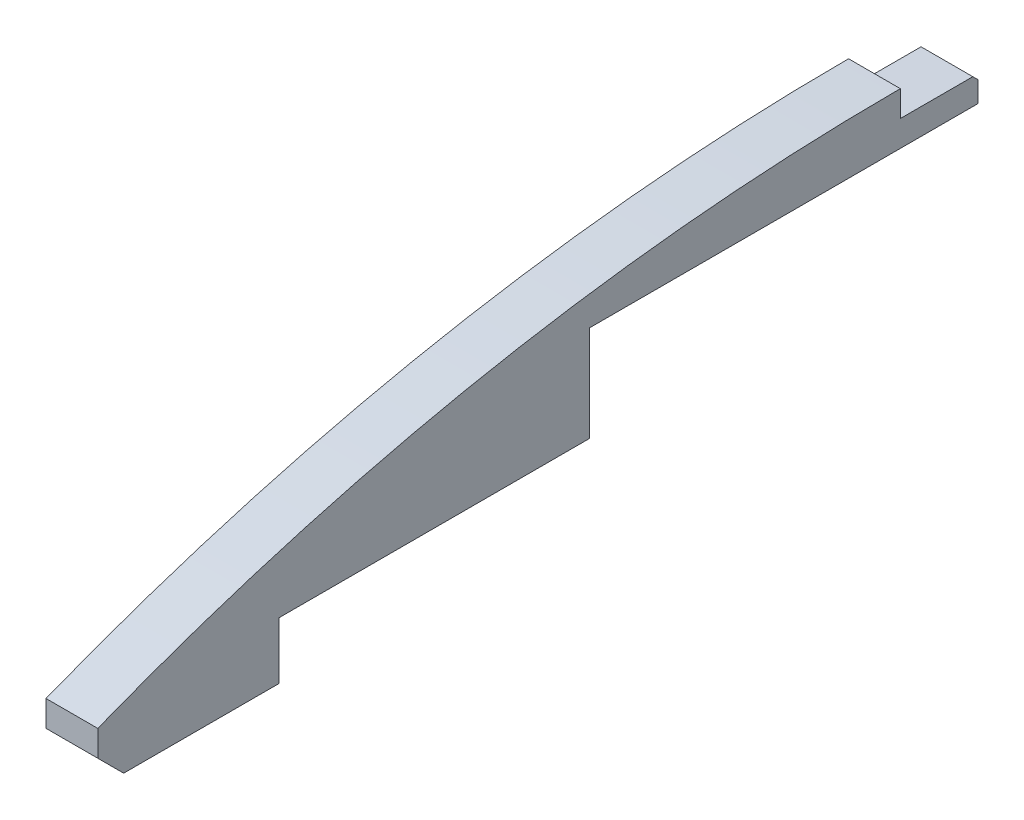
SolidWorks part; units mm, degrees
material "ABS"
ref_plane "Front" through (0, 0, 0) normal (0, 0, 1) x (1, 0, 0)
ref_plane "Top" through (0, 0, 0) normal (0, 1, 0) x (1, 0, 0)
ref_plane "Right" through (0, 0, 0) normal (1, 0, 0) x (0, 0, -1)
sketch "Sketch1" plane through (0, 0, 0) normal (1, 0, 0) x (0, 0, -1)
  line L0 (0, 0) -> (0, 43.5) construction
  line L1 (0, 0) -> (-186.595, 0) construction
  line L2 (-155, 14) -> (-155, 9)
  line L3 (-155, 9) -> (-150, 4)
  line L4 (-150, 4) -> (-120, 4)
  line L5 (-120, 4) -> (-120, 15)
  line L6 (-120, 15) -> (-60, 15)
  line L7 (-60, 15) -> (-60, 33.5)
  line L8 (0, 43.5) -> (0, 38.5)
  line L9 (0, 38.5) -> (14, 38.5)
  line L10 (15, 37.5) -> (15, 33.5)
  line L11 (15, 33.5) -> (-60, 33.5)
  line L13 (14, 38.5) -> (15, 37.5)
  arc A0 (0, 43.5) -> (-186.595, 0) centre (0, -378.4534) ccw construction
  arc A1 (0, 43.5) -> (-155, 14) centre (0, -378.4534) ccw
  point P13 (15, 38.5)
  dimension "D1" = 43.5
  dimension "D2" = 170
  dimension "D3" = 5
  dimension "D4" = 5
  dimension "D5" = 4
  dimension "D6" = 45
  dimension "D7" = 15
  dimension "D8" = 60
  dimension "D9" = 30
  dimension "D10" = 38.5
  dimension "D12" = 5
  dimension "D13" = 15
  dimension "D17" = 1
revolve "Revolve1" [suppressed] add sketch "Sketch1" angle 360 about L1
extrude "Extrude1" add sketch "Sketch1<2>" along normal blind 10
sketch "Sketch1<2>" plane through (0, 0, 0) normal (1, 0, 0) x (0, 0, -1) same geometry as "Sketch1"
